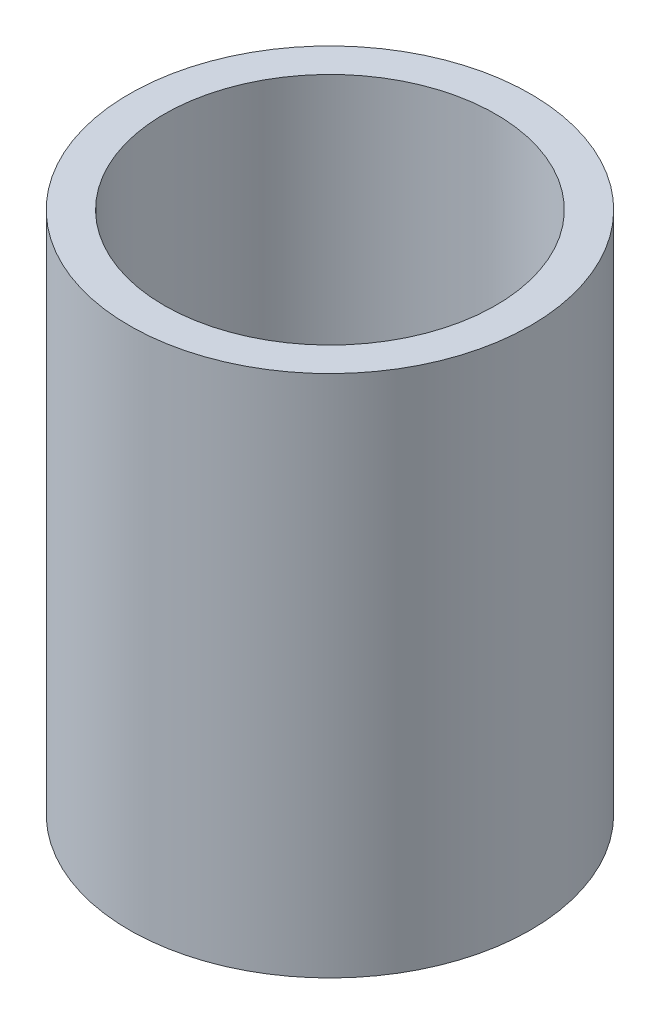
SolidWorks part; units mm, degrees
ref_plane "Спереди" through (0, 0, 0) normal (0, 0, 1) x (1, 0, 0)
ref_plane "Сверху" through (0, 0, 0) normal (0, 1, 0) x (1, 0, 0)
ref_plane "Справа" through (0, 0, 0) normal (1, 0, 0) x (0, 0, -1)
sketch "Эскиз1" plane through (0, 0, 0) normal (0, 1, 0) x (1, 0, 0)
  circle A0 centre (0, 0) radius 47.5
extrude "Вытянуть-Тонкостенный1" add sketch "Эскиз1" along normal blind 150 thin thin type one direction wall 10
